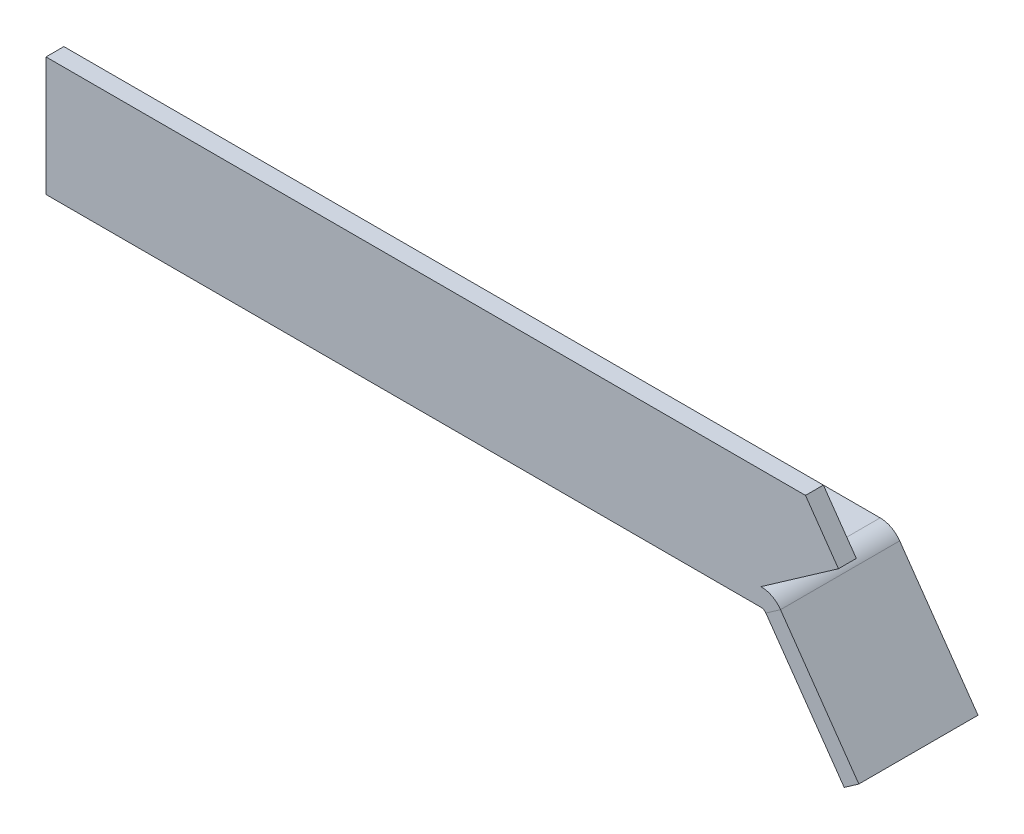
SolidWorks part; units mm, degrees
note: The reader was unsure of these and kept them because the rebuilt part matched: flange length of "Ребро-кромка2".
ref_plane "Спереди" through (0, 0, 0) normal (0, 0, 1) x (1, 0, 0)
ref_plane "Сверху" through (0, 0, 0) normal (0, 1, 0) x (1, 0, 0)
ref_plane "Справа" through (0, 0, 0) normal (1, 0, 0) x (0, 0, -1)
sketch "Эскиз1" plane through (0, 0, 0) normal (1, 0, 0) x (0, 0, -1)
  line L0 (0, 20) -> (0, 0)
  line L1 (0, 0) -> (20, 0)
extrude "Вытянуть-Тонкостенный1" add sketch "Эскиз1" along normal blind 120 thin thin type one direction reverse wall 3
sketch "Эскиз3" plane through (0, 0, 0) normal (0, -1, 0) x (1, 0, 0)
  line L1 (0, 0) -> (120, 0)
  line L2 (0, 0) -> (0, -20)
  line L3 (0, -20) -> (120, -20)
  line L4 (120, 0) -> (120, -20)
base flange "Базовая кромка1" sketch "Эскиз3" thickness 3 reverse thickness direction no parameters "D1"=3
edge flange "Ребро-кромка2" sketch "Эскиз9" flange angle 125 flange length 25 flange position bend outside bend radius 1 thickness 3 parameters "D6"=10
sketch "Эскиз9" plane through (120, 0, 0) normal (-0.8192, -0.5736, 0) x (0, 0, -1)
  line L2 (0, 0) -> (0, 23.4383)
  line L3 (0, 23.4383) -> (20, 23.4383)
  line L4 (20, 23.4383) -> (20, 0)
  line L5 (20, 0) -> (0, 0) construction
  line L6 (20, 0) -> (0, 0)
bend "EdgeBend1" bend radius 1 bend angle 55 parameters "D5"=1
sketch "Эскиз10" plane through (0, 0, 0) normal (0, 0, 1) x (1, 0, 0)
  line L0 (120, 20) -> (120, 3)
  line L1 (120, 3) -> (133, 12.1027)
  line L2 (133, 12.1027) -> (127.4702, 20)
  line L3 (127.4702, 20) -> (120, 20)
extrude "Бобышка-Вытянуть1" add sketch "Эскиз10" against normal blind 3
sketch "Сгиб-Линии1" [suppressed] plane through (0, 0, 0) normal (0, 1, 0) x (1, 0, 0)
sketch "Граничная рамка1" [suppressed] plane through (0, 0, 0) normal (0, 1, 0) x (1, 0, 0)
sheet metal parameters "Листовой металл2" thickness 3 parameters "D1"=3
flat pattern "Развертка2" [suppressed]
sketch "Сгиб-Линии2" plane through (0, 0, 0) normal (0, 1, 0) x (1, 0, 0)
sketch3d "Граничная рамка2" [suppressed]
  line L0 (-140, 20, 0) -> (0, 20, 0) construction
  line L1 (-140, 0, 0) -> (0, 0, 0) construction
  line L2 (-140, 20, 0) -> (-140, 0, 0) construction
  line L3 (0, 20, 0) -> (0, 0, 0) construction
sheet metal parameters "Листовой металл7" thickness 3 parameters "D1"=3
flat pattern "Развертка2"
sketch "Сгиб-Линии2" plane through (0, 0, 0) normal (0, -1, 0) x (-1, 0, 0)
  line L0 (-142.8798, 0) -> (-142.8798, 20) construction
  line L1 (-142.8798, 0) -> (-142.8798, 20) construction
sketch3d "Граничная рамка2" [suppressed]
  line L0 (-165.6362, 20, 0) -> (0, 20, 0) construction
  line L1 (-165.6362, 0, 0) -> (0, 0, 0) construction
  line L2 (-165.6362, 20, 0) -> (-165.6362, 0, 0) construction
  line L3 (0, 20, 0) -> (0, 0, 0) construction
bend of the flat pattern "Плоское состояние-<EdgeBend1>1"
sheet metal parameters "Листовой металл8" thickness 3 parameters "D1"=3
flat pattern "Развертка2"
sketch "Сгиб-Линии2" plane through (0, 0, 0) normal (0, -1, 0) x (-1, 0, 0)
  line L0 (-142.8798, 0) -> (-142.8798, 20) construction
  line L1 (-142.8798, 0) -> (-142.8798, 20) construction
sketch3d "Граничная рамка2" [suppressed]
  line L0 (-165.6362, 20, 0) -> (0, 20, 0) construction
  line L1 (-165.6362, 0, 0) -> (0, 0, 0) construction
  line L2 (-165.6362, 20, 0) -> (-165.6362, 0, 0) construction
  line L3 (0, 20, 0) -> (0, 0, 0) construction
bend of the flat pattern "Плоское состояние-<EdgeBend1>1"
